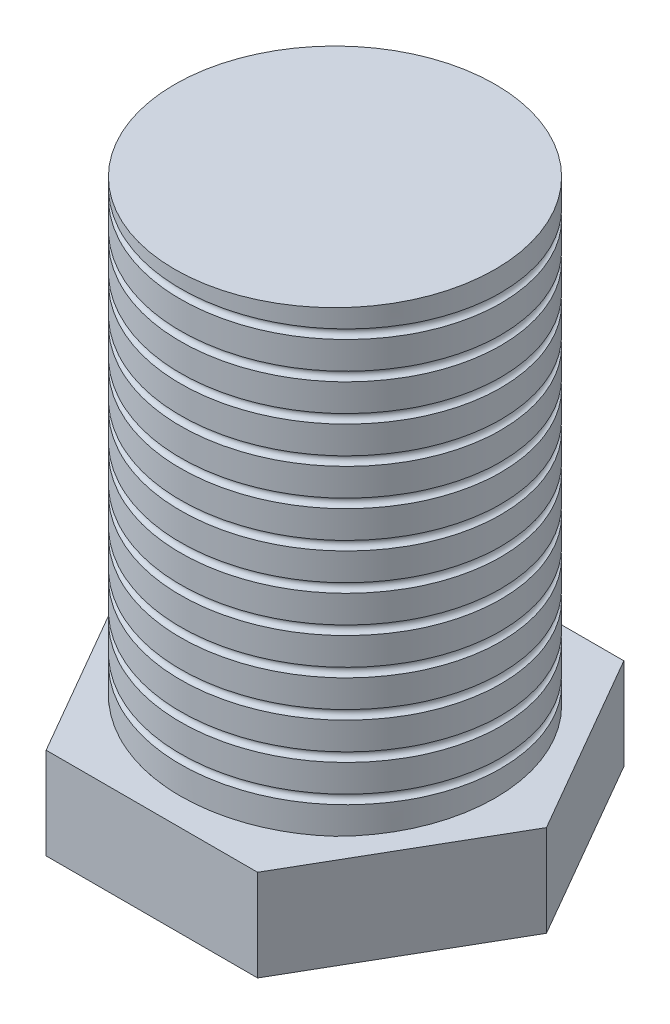
SolidWorks part; units mm, degrees
ref_plane "Front Plane" through (0, 0, 0) normal (0, 0, 1) x (1, 0, 0)
ref_plane "Top Plane" through (0, 0, 0) normal (0, 1, 0) x (1, 0, 0)
ref_plane "Right Plane" through (0, 0, 0) normal (1, 0, 0) x (0, 0, -1)
sketch "Sketch2" plane through (0, 0, 0) normal (0, 1, 0) x (1, 0, 0)
  circle A0 centre (0, 0) radius 3.5
  dimension "D1" = 7
ref_plane "Plane2" through (0, 68, 0) normal (0, 1, 0) x (1, 0, 0)
ref_plane "Plane3" through (0, 17.5, 0) normal (0, 1, 0) x (1, 0, 0)
sketch "Sketch8" plane through (0, 0, 0) normal (0, 1, 0) x (1, 0, 0)
  circle A0 centre (0, 0) radius 0.35
  dimension "D1" = 0.7
curve "Helix/Spiral2" pitch 0.8 height 10 radius 0.35 left hand yes centre (0, 0, 0) axis (0, 1, 0) start towards (1, 0, 0)
extrude "Boss-Extrude2" add sketch "Sketch2" along normal blind 10
sketch "Sketch9" plane through (0, 0, 0) normal (1, 0, 0) x (0, 0, -1)
  circle A0 centre (-3.5, 0) radius 0.1
  dimension "D1" = 0.2
sweep "Cut-Sweep2" cut profiles "Sketch9" path "Helix/Spiral2"
sketch "Sketch10" plane through (0, 0, 0) normal (0, -1, 0) x (1, 0, 0)
  line L1 (-4.6188, 0) -> (-2.3094, -4)
  line L2 (-2.3094, -4) -> (2.3094, -4)
  line L3 (2.3094, -4) -> (4.6188, 0)
  line L4 (4.6188, 0) -> (2.3094, 4)
  line L5 (2.3094, 4) -> (-2.3094, 4)
  line L6 (-2.3094, 4) -> (-4.6188, 0)
  circle A0 centre (0, 0) radius 4 construction
  dimension "D1" = 4
extrude "Boss-Extrude3" add sketch "Sketch10" along normal blind 2
